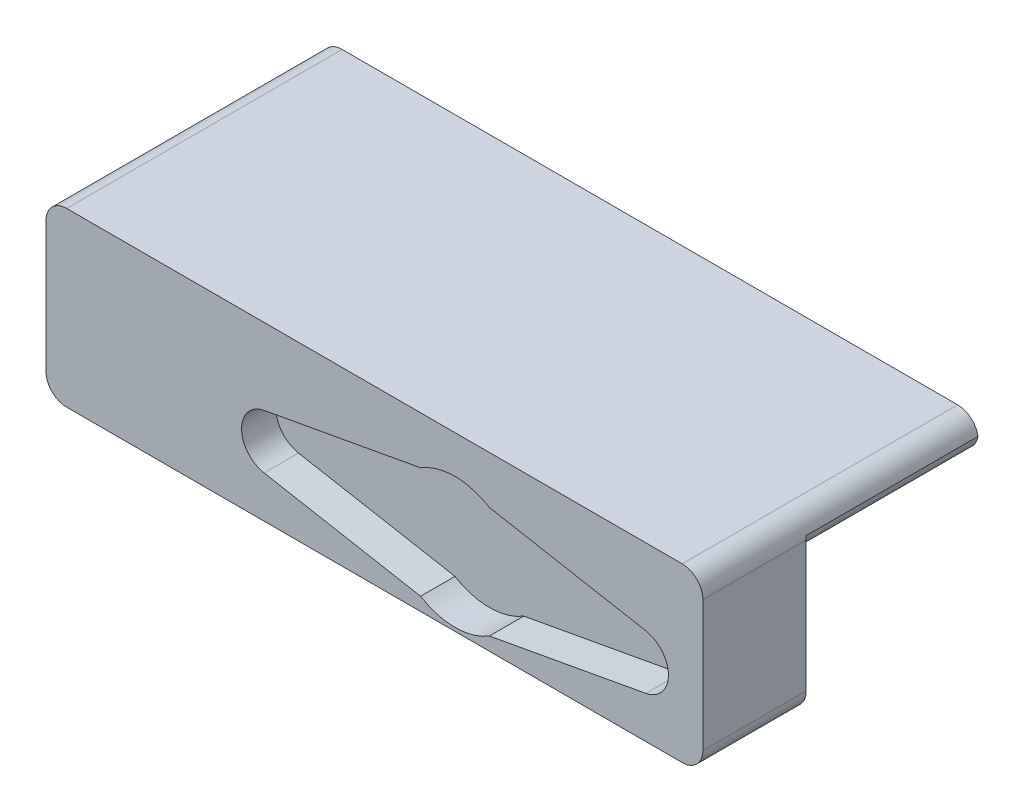
SolidWorks part; units mm, degrees
ref_plane "Front Plane" through (0, 0, 0) normal (0, 0, 1) x (1, 0, 0)
ref_plane "Top Plane" through (0, 0, 0) normal (0, 1, 0) x (1, 0, 0)
ref_plane "Right Plane" through (0, 0, 0) normal (1, 0, 0) x (0, 0, -1)
sketch "Sketch1" plane through (0, 0, 0) normal (0, 0, 1) x (1, 0, 0)
  line L1 (-37.719, -6.35) -> (37.719, -6.35)
  line L2 (-37.719, -6.35) -> (-37.719, 6.35)
  line L3 (-37.719, 6.35) -> (37.719, 6.35)
  line L4 (37.719, -6.35) -> (37.719, 6.35)
  line L5 (0, 6.35) -> (0, -6.35) construction
  line L6 (-37.719, 0) -> (37.719, 0) construction
  point P0 (0, 0)
  dimension "D1" = 75.438
  dimension "D2" = 12.7
extrude "Boss-Extrude1" add sketch "Sketch1" along normal blind 6.35
sketch "Sketch2" plane through (0, 0, 6.35) normal (0, 0, 1) x (1, 0, 0)
  line L1 (0, 0) -> (3.175, 5.1294) construction
  line L2 (0, -1000) -> (0, 49000) construction
  line L3 (3.175, 5.1294) -> (17.6007, 2.4988)
  line L4 (-1000, 0) -> (49000, 0) construction
  line L5 (3.175, -5.1294) -> (17.6007, -2.4988)
  line L6 (-3.175, -5.1294) -> (-17.6007, -2.4988)
  line L7 (-3.175, 5.1294) -> (-17.6007, 2.4988)
  arc A0 (-3.175, -5.1294) -> (3.175, -5.1294) centre (0, 0) ccw
  arc A1 (17.6007, -2.4988) -> (17.6007, 2.4988) centre (17.145, 0) ccw
  arc A2 (-17.6007, -2.4988) -> (-17.6007, 2.4988) centre (-17.145, 0) cw
  arc A3 (3.175, 5.1294) -> (-3.175, 5.1294) centre (0, 0) ccw
  dimension "D1" = 12.065
  dimension "D2" = 5.08
  dimension "D3" = 17.145
  dimension "D4" = 3.175
extrude "Cut-Extrude1" cut sketch "Sketch2" against normal blind 3.175
sketch "Sketch3" plane through (0, 0, 0) normal (0, 1, 0) x (1, 0, 0)
  line L0 (-34.544, 3.175) -> (34.544, 3.175)
  line L1 (-37.719, 0) -> (37.719, 0)
  line L2 (-37.719, 0) -> (-37.719, 19.05)
  line L3 (-37.719, 19.05) -> (37.719, 19.05)
  line L4 (37.719, 0) -> (37.719, 19.05)
  line L5 (34.544, 3.175) -> (34.544, 15.875)
  line L6 (-34.544, 15.875) -> (34.544, 15.875)
  line L7 (-34.544, 3.175) -> (-34.544, 15.875)
  dimension "D2" = 19.05
  dimension "D1" = 3.175
extrude "Boss-Extrude2" add sketch "Sketch3" along normal up to surface and the other way up to surface up to face at (0, 6.35, 3.175) other way up to face at (0, -6.35, 3.175)
sketch "Sketch4" plane through (0, 6.35, 0) normal (0, 1, 0) x (1, 0, 0)
  line L0 (-37.719, -6.35) -> (-37.719, 19.05) construction
  line L1 (-37.719, -6.35) -> (37.719, -6.35)
  line L2 (-37.719, -6.35) -> (-37.719, 19.05)
  line L3 (-37.719, 19.05) -> (37.719, 19.05)
  line L4 (37.719, -6.35) -> (37.719, 19.05)
  point P7 (-37.719, -6.35)
extrude "Boss-Extrude4" add sketch "Sketch4" along normal blind 3.175
sketch "Sketch7" plane through (0, 0, 6.35) normal (0, 0, 1) x (1, 0, 0)
  line L0 (-37.719, 9.525) -> (37.719, 9.525) construction
  line L1 (37.719, -6.35) -> (22.86, -6.35)
  line L2 (37.719, -6.35) -> (37.719, 9.525)
  line L3 (37.719, 9.525) -> (22.86, 9.525)
  line L4 (22.86, -6.35) -> (22.86, 9.525)
  arc A0 (17.6007, -2.4988) -> (17.6007, 2.4988) centre (17.145, 0) ccw construction
  point P10 (19.685, 0)
  dimension "D1" = 3.175
extrude "Cut-Extrude3" cut sketch "Sketch7" against normal through all
sketch "Sketch8" plane through (22.86, 0, 0) normal (1, 0, 0) x (0, 0, -1)
  line L1 (15.875, -6.35) -> (19.05, -6.35)
  line L2 (15.875, -6.35) -> (15.875, 9.525)
  line L3 (15.875, 9.525) -> (19.05, 9.525)
  line L4 (19.05, -6.35) -> (19.05, 9.525)
extrude "Cut-Extrude4" cut sketch "Sketch8" against normal through all
sketch "Sketch9" plane through (0, 0, -15.875) normal (0, 0, -1) x (-1, 0, 0)
  line L6 (34.544, 6.35) -> (34.544, -6.35)
  line L7 (34.544, -6.35) -> (37.719, -6.35)
  line L8 (37.719, -6.35) -> (37.719, 9.525)
  line L9 (37.719, 9.525) -> (-22.86, 9.525)
  line L10 (-22.86, 9.525) -> (-22.86, 6.35)
  line L11 (-22.86, 6.35) -> (34.544, 6.35)
  line L12 (34.544, 6.35) -> (34.544, -6.35)
  line L13 (34.544, -6.35) -> (37.719, -6.35)
  line L14 (37.719, -6.35) -> (37.719, 9.525)
  line L15 (37.719, 9.525) -> (-22.86, 9.525)
  line L16 (-22.86, 9.525) -> (-22.86, 6.35)
  line L17 (-22.86, 6.35) -> (34.544, 6.35)
  dimension "D1" = 0
extrude "Boss-Extrude5" add sketch "Sketch9" along normal blind 3.175
fillet "Fillet2" radius 1.905 7 edges at (-37.719, 9.525, -6.35) (-34.544, 6.35, -11.1125) (-37.719, -6.35, -6.35) (-34.544, -6.35, -11.1125) (22.86, 6.35, -11.1125) (22.86, 9.525, -6.35) (22.86, -6.35, 1.5875)
sketch "Sketch10" plane through (0, 6.35, 0) normal (0, -1, 0) x (1, 0, 0)
  circle A0 centre (-29.4146, -11.1125) radius 1.3307
  circle A1 centre (-26.1537, -11.1125) radius 1.2369
